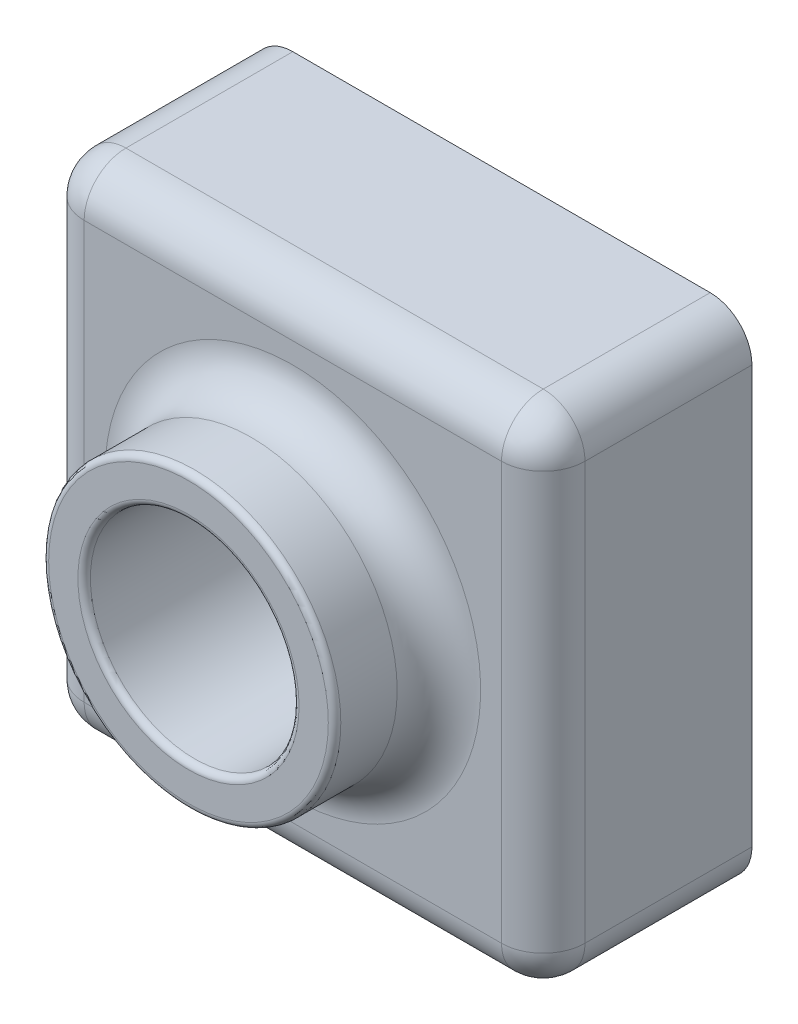
SolidWorks part; units mm, degrees
material "Acero inoxidable al cromo"
ref_plane "Alzado" through (0, 0, 0) normal (0, 0, 1) x (1, 0, 0)
ref_plane "Planta" through (0, 0, 0) normal (0, 1, 0) x (1, 0, 0)
ref_plane "Vista lateral" through (0, 0, 0) normal (1, 0, 0) x (0, 0, -1)
sketch "Croquis2" plane through (0, 0, 0) normal (0, 0, 1) x (1, 0, 0)
  line L1 (0, 0) -> (120, 0)
  line L2 (0, 0) -> (0, 120)
  line L3 (0, 120) -> (120, 120)
  line L4 (120, 0) -> (120, 120)
  dimension "D1" = 120
  dimension "D2" = 120
extrude "Saliente-Extruir1" add sketch "Croquis2" along normal blind 50
sketch "Croquis3" plane through (0, 0, 50) normal (0, 0, 1) x (1, 0, 0)
  line L0 (120, 120) -> (0, 120) construction
  line L1 (120, 0) -> (120, 120) construction
  circle A0 centre (60, 60) radius 35
  dimension "D1" = 70
  dimension "D2" = 60
  dimension "D3" = 60
extrude "Saliente-Extruir2" add sketch "Croquis3" along normal blind 25
sketch "Croquis6" plane through (0, 0, 75) normal (0, 0, 1) x (1, 0, 0)
  line L0 (120, 120) -> (0, 120) construction
  line L1 (120, 0) -> (120, 120) construction
  circle A0 centre (60, 60) radius 25
  point P2 (0, 0)
  point P3 (60, 120)
  dimension "D1" = 50
  dimension "D2" = 60
  dimension "D3" = 60
extrude "Saliente-Extruir3" add sketch "Croquis6" against normal through all
extrude "Cortar-Extruir1" cut sketch "Croquis6<2>" against normal through all
sketch "Croquis6<2>" plane through (0, 0, 75) normal (0, 0, 1) x (1, 0, 0) same geometry as "Croquis6"
fillet "Redondeo1" radius 10 9 edges at (25, 60, 50) (60, 120, 50) (120, 60, 50) (60, 0, 50) (0, 60, 50) (0, 120, 25) (0, 0, 25) (120, 0, 25) (120, 120, 25)
fillet "Redondeo2" radius 1.5 2 edges at (95, 60, 75) (85, 60, 75)
shell "Vaciado1" thickness 2 removed face at (85, 60, 0)
